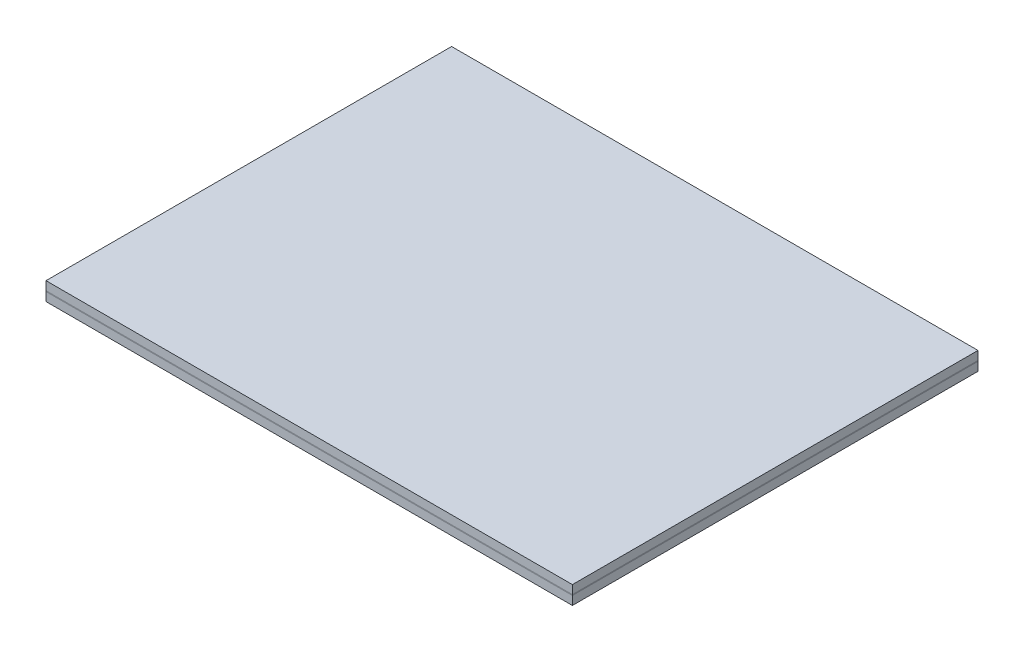
SolidWorks part; units mm, degrees
ref_plane "Front Plane" through (0, 0, 0) normal (0, 0, 1) x (1, 0, 0)
ref_plane "Top Plane" through (0, 0, 0) normal (0, 1, 0) x (1, 0, 0)
ref_plane "Right Plane" through (0, 0, 0) normal (1, 0, 0) x (0, 0, -1)
sketch "Sketch1" plane through (0, 0, 0) normal (0, 1, 0) x (1, 0, 0)
  line L1 (-27.5685, 15.0941) -> (33.4315, 15.0941)
  line L2 (-27.5685, 15.0941) -> (-27.5685, -31.9059)
  line L3 (-27.5685, -31.9059) -> (33.4315, -31.9059)
  line L4 (33.4315, 15.0941) -> (33.4315, -31.9059)
  dimension "D1" = 61
  dimension "D2" = 47
extrude "Boss-Extrude1" add sketch "Sketch1" along normal blind 1
sketch "Sketch2" plane through (0, 1, 0) normal (0, 1, 0) x (1, 0, 0)
  line L0 (-25.0685, 13.5941) -> (-25.0685, -30.4059)
  line L1 (-25.0685, -30.4059) -> (31.9315, -30.4059)
  line L2 (31.9315, -30.4059) -> (31.9315, 13.5941)
  line L3 (31.9315, 13.5941) -> (-25.0685, 13.5941)
  line L4 (-27.5685, 15.0941) -> (33.4315, 15.0941)
  line L5 (33.4315, 15.0941) -> (33.4315, -31.9059)
  line L6 (33.4315, -31.9059) -> (-27.5685, -31.9059)
  line L7 (-27.5685, -31.9059) -> (-27.5685, 15.0941)
  dimension "D1" = 1.5
  dimension "D2" = 1.5
  dimension "D3" = 1.5
  dimension "D4" = 2.5
extrude "Boss-Extrude5" add sketch "Sketch2" along normal blind 0.1 separate body
extrude "Boss-Extrude3" add sketch "Sketch1<3>" along normal blind 1 from surface separate body starting at face at (2.9315, 1.1, 8.4059)
sketch "Sketch1<3>" plane through (0, 0, 0) normal (0, 1, 0) x (1, 0, 0) same geometry as "Sketch1"
